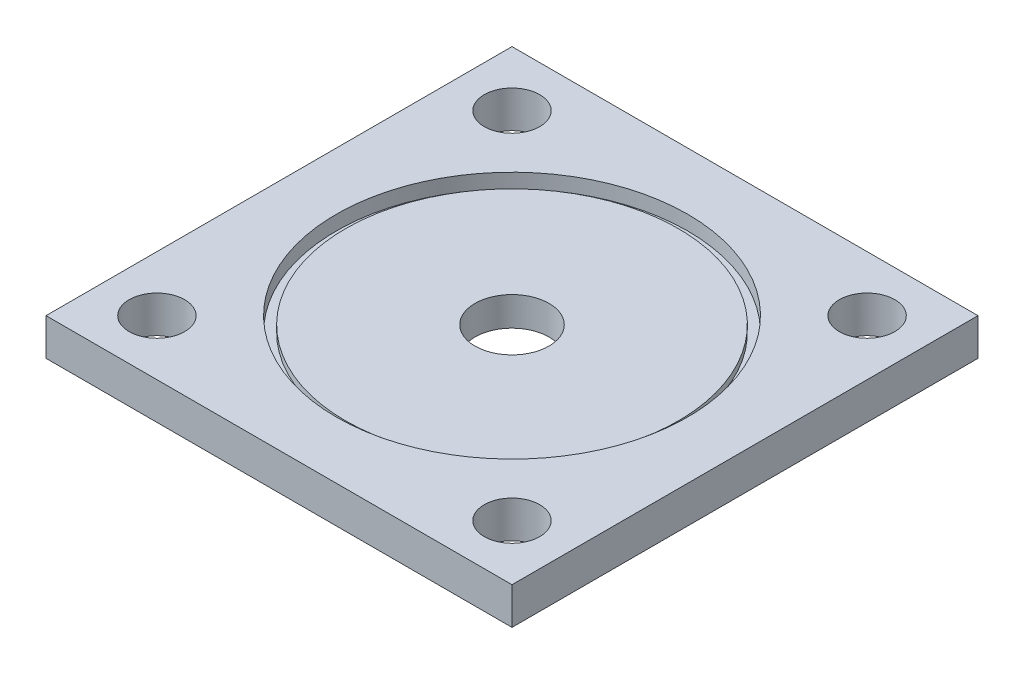
SolidWorks part; units mm, degrees
ref_plane "Front Plane" through (0, 0, 0) normal (0, 0, 1) x (1, 0, 0)
ref_plane "Top Plane" through (0, 0, 0) normal (0, 1, 0) x (1, 0, 0)
ref_plane "Right Plane" through (0, 0, 0) normal (1, 0, 0) x (0, 0, -1)
sketch "plateOutline" plane through (0, 0, 0) normal (0, 1, 0) x (1, 0, 0)
  line L1 (-40, -40) -> (40, -40)
  line L2 (-40, -40) -> (-40, 40)
  line L3 (-40, 40) -> (40, 40)
  line L4 (40, -40) -> (40, 40)
  line L5 (-40, -40) -> (40, 40) construction
  line L6 (-40, 40) -> (40, -40) construction
  line L7 (-40, -40) -> (40, -40) construction
  line L8 (-40, -40) -> (-40, 40) construction
  line L9 (-40, 40) -> (40, 40) construction
  line L10 (40, -40) -> (40, 40) construction
  point P0 (0, 0)
  dimension "D1" = 80
sketch "railGuides" plane through (0, 0, 0) normal (0, 1, 0) x (1, 0, 0)
  line L0 (-30.48, 30.48) -> (30.48, 30.48) construction
  line L1 (30.48, -30.48) -> (30.48, 30.48) construction
  line L2 (-30.48, -30.48) -> (30.48, -30.48) construction
  line L3 (-30.48, -30.48) -> (-30.48, 30.48) construction
  line L5 (-40.005, -40.005) -> (40.005, -40.005) construction
  line L11 (-40.005, -40.005) -> (-40.005, 40.005) construction
  line L12 (-40.005, 40.005) -> (40.005, 40.005) construction
  line L13 (40.005, -40.005) -> (40.005, 40.005) construction
  line L14 (-40.005, -40.005) -> (40.005, 40.005) construction
  line L15 (-40.005, 40.005) -> (40.005, -40.005) construction
  circle A0 centre (-30.48, 30.48) radius 4.7625
  circle A1 centre (30.48, 30.48) radius 4.7625
  circle A2 centre (30.48, -30.48) radius 4.7625
  circle A3 centre (-30.48, -30.48) radius 4.7625
  point P1 (0, 0)
  dimension "D1" = 80.01
  dimension "D3" = 9.525
  dimension "D4" = 9.525
  dimension "D5" = 9.525
  dimension "D6" = 9.525
  dimension "D7" = 9.525
  dimension "D2" = 80.01
sketch "FuelGrainMounting" plane through (0, 0, 0) normal (0, 1, 0) x (1, 0, 0)
  circle A0 centre (0, 0) radius 30.1625
  dimension "D1" = 60.325
sketch "GasIntake" plane through (0, 0, 0) normal (0, 1, 0) x (1, 0, 0)
  line L0 (-40, 40) -> (40, -40) construction
  circle A0 centre (0, 0) radius 6.35
  dimension "D1" = 12.7
extrude "Boss-Extrude1" add sketch "plateOutline" along normal blind 6.35 contours L3 L4 L1 L2
extrude "Cut-Extrude1" cut sketch "railGuides" along normal blind 10 contours A0 | A3 | A1 | A2 region at (-30.48, 0, -30.48)
extrude "Cut-Extrude2" cut sketch "FuelGrainMounting" along normal blind 5 from offset 5
extrude "Cut-Extrude3" cut sketch "GasIntake" along normal blind 5
sketch "Sketch1" plane through (0, 0, 0) normal (0, 1, 0) x (1, 0, 0)
  circle A0 centre (0, 0) radius 28.575
  circle A2 centre (0, 0) radius 30.1625
  dimension "D1" = 60.325
  dimension "D2" = 57.15
extrude "Cut-Extrude4" cut sketch "Sketch1" against normal blind 1.143 from offset 5
